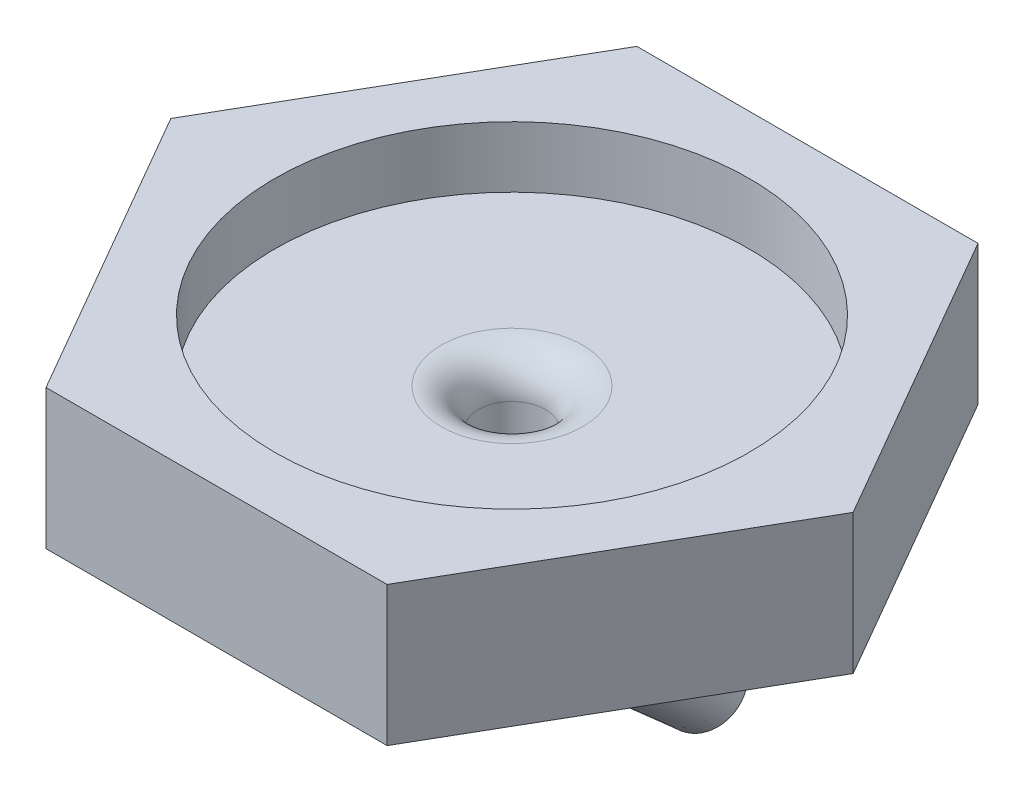
SolidWorks part; units mm, degrees
ref_plane "Front Plane" through (0, 0, 0) normal (0, 0, 1) x (1, 0, 0)
ref_plane "Top Plane" through (0, 0, 0) normal (0, 1, 0) x (1, 0, 0)
ref_plane "Right Plane" through (0, 0, 0) normal (1, 0, 0) x (0, 0, -1)
sketch "Sketch11" plane through (0, 0, 0) normal (0, 1, 0) x (1, 0, 0)
  line L7 (18.3309, 0) -> (9.1654, 15.875)
  line L8 (9.1654, 15.875) -> (-9.1654, 15.875)
  line L9 (-9.1654, 15.875) -> (-18.3309, 0)
  line L10 (-18.3309, 0) -> (-9.1654, -15.875)
  line L11 (-9.1654, -15.875) -> (9.1654, -15.875)
  line L12 (9.1654, -15.875) -> (18.3309, 0)
  circle A0 centre (0, 0) radius 15.875 construction
  dimension "D1" = 31.75
extrude "MainHolder" add sketch "Sketch11" along normal blind 7.5
sketch "Sketch12" plane through (0, 7.5, 0) normal (0, 1, 0) x (1, 0, 0)
  circle A0 centre (0, 0) radius 12.75
  dimension "D1" = 25.5
extrude "MagnetCutout" cut sketch "Sketch12" against normal blind 3.28
sketch "Sketch13" plane through (0, 4.22, 0) normal (0, 1, 0) x (1, 0, 0)
  circle A0 centre (0, 0) radius 1.8
  dimension "D1" = 3.6
extrude "MagnetHole" cut sketch "Sketch13" against normal up to next
sketch "DrainPath" plane through (0, 0, 0) normal (1, 0, 0) x (0, 0, -1)
  line L0 (0, 0) -> (0, -2)
  line L1 (1.7574, -6.2426) -> (10.2426, -14.7279)
  arc A0 (1.7574, -6.2426) -> (0, -2) centre (6, -2) cw
  point P7 (0, -4.4853)
  dimension "D3" = 6
  dimension "D1" = 135
  dimension "D2" = 12
  dimension "D4" = 2
sketch "DrainOpening" plane through (0, 0, 0) normal (0, -1, 0) x (1, 0, 0)
  circle A0 centre (0, 0) radius 1.125
  circle A2 centre (0, 0) radius 2
  dimension "D1" = 2.25
  dimension "D2" = 4
sweep "Drain" add profiles "DrainOpening" path "DrainPath"
ref_axis "DrainOutAxis" through (0, -5.4471, -0.9619) along (0, -0.7071, -0.7071)
ref_plane "DrainMidPlain" through (0, 0, 0) normal (-1, 0, 0) x (0, -0.7071, -0.7071)
sketch "BarbOutline" plane through (0, 0, 0) normal (-1, 0, 0) x (0, -0.7071, -0.7071)
  line L0 (17.6569, 1.1716) -> (11.6569, 1.1716)
  line L1 (11.6569, 1.1716) -> (11.6569, 0.7966)
  line L2 (11.6569, 0.7966) -> (17.6569, 1.1716)
  line L3 (5.6569, 1.1716) -> (17.6569, 1.1716) construction
  line L4 (4.5319, 3.1716) -> (18.7819, 3.1716) construction
  line L8 (5.6569, 1.1716) -> (17.6569, 1.1716) construction
  dimension "D1" = 6
  dimension "D2" = 2.375
revolve "Barb" add sketch "BarbOutline" angle 360 about axis through (0, -5.4471, -0.9619) along (0, -0.7071, -0.7071)
ref_axis "MagnetAxis" through (0, 0, 0) along (0, 1, 0)
fillet "DrainBaseFillet" radius 2 1 edges at (0, 4.22, 1.8) type face fillet first side face at (0, 4.22, 1.8) second side face at (0, 4.22, 1.8)
fillet "DrainBottomFillet" radius 2 1 edges at (0, 0, -2) type face fillet first side face at (0, 0, -2) second side face at (0, -2, -2)
fillet "BarbFillet" radius 1 1 edges at (0, -11.8995, -4.5858)
equation "\"channel_diameter\" = 4mm"
equation "\"channel_length\"= 12mm"
equation "\"barb_length\"= 6mm"
equation "\"lumen_diameter\" = 2.25mm"
equation "\"magnet_holder_thickness\"= 7.5"
equation "\"magnet_diameter\"=25.4"
equation "\"magnet_holder_tolerance\"= 0.1mm"
equation "\"magnet_thickness\"= 3.18mm"
equation "\"D1@Sketch11\"=\"magnet_diameter\" * 1.25"
equation "\"D1@MainHolder\" = \"magnet_holder_thickness\""
equation "\"D1@Sketch12\"=\"magnet_diameter\" + \"magnet_holder_tolerance\""
equation "\"D1@MagnetCutout\" = \"magnet_thickness\" + \"magnet_holder_tolerance\""
equation "\"magnet_hole_small\"= 4.83mm"
equation "\"D1@Sketch13\"=\"channel_diameter\" * 0.9"
equation "\"drain_angle\"= 135"
equation "\"D1@DrainPath\" = \"drain_angle\""
equation "\"D2@DrainPath\" = \"barb_length\" * 2"
equation "\"D1@DrainOpening\" = \"lumen_diameter\""
equation "\"D1@BarbOutline\" = \"barb_length\""
equation "\"D2@BarbOutline\"=\"channel_diameter\" / 2 + \"barb_extension\""
equation "\"FilletBase\"=3"
equation "\"barb_extension\"= 0.75mm / 2"
equation "\"D2@DrainOpening\"=\"channel_diameter\""
